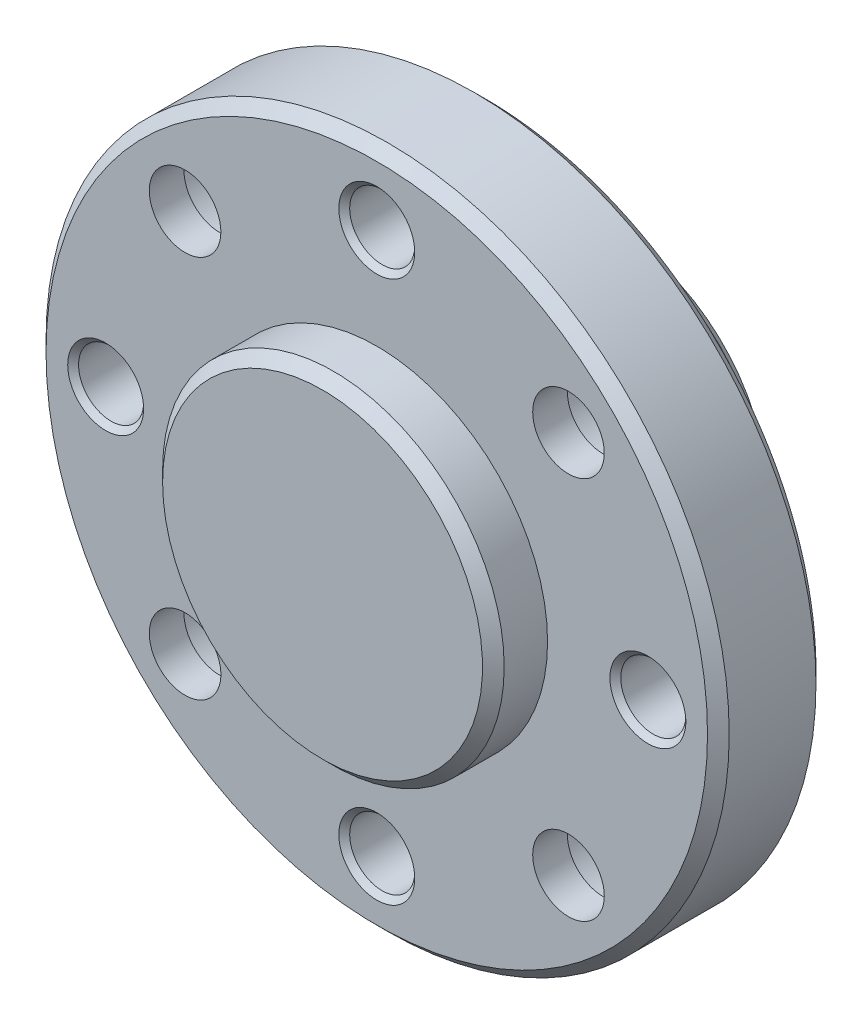
SolidWorks part; units mm, degrees
material "7050-T73510"
ref_plane "前视基准面" through (0, 0, 0) normal (0, 0, 1) x (1, 0, 0)
ref_plane "上视基准面" through (0, 0, 0) normal (0, 1, 0) x (1, 0, 0)
ref_plane "右视基准面" through (0, 0, 0) normal (1, 0, 0) x (0, 0, -1)
sketch "草图1" plane through (0, 0, 0) normal (1, 0, 0) x (0, 0, -1)
  line L0 (-27.0993, 0) -> (42.7335, 0) construction
  line L1 (0, 0) -> (0, 15.75)
  line L2 (0, 15.75) -> (5, 15.75)
  line L3 (5, 15.75) -> (5, 31.5)
  line L4 (5, 31.5) -> (15, 31.5)
  line L5 (15, 31.5) -> (15, 15)
  line L6 (15, 15) -> (27, 15)
  line L7 (27, 15) -> (27, 10)
  line L8 (27, 10) -> (3, 10)
  line L9 (3, 10) -> (3, 0)
  line L10 (3, 0) -> (0, 0)
  dimension "D1" = 31.5
  dimension "D2" = 5
  dimension "D3" = 63
  dimension "D4" = 10
  dimension "D5" = 30
  dimension "D6" = 20
  dimension "D7" = 3
  dimension "D8" = 24
revolve "旋转1" add sketch "草图1" angle 360 about L0
sketch "草图2" plane through (0, 0, -15) normal (0, 0, -1) x (-1, 0, 0)
  line L0 (-39.8585, 0) -> (40.5821, 0) construction
  line L1 (0, 34.2021) -> (0, -33.8732) construction
  line L2 (-17.6777, 17.6777) -> (0, 0) construction
  circle A0 centre (-17.6777, 17.6777) radius 5.5
  circle A1 centre (-17.6777, 17.6777) radius 3.3
  circle A2 centre (0, 0) radius 25 construction
  circle A3 centre (0, 25) radius 3
  circle A4 centre (17.6777, 17.6777) radius 5.5
  circle A5 centre (17.6777, 17.6777) radius 3.3
  circle A6 centre (17.6777, -17.6777) radius 3.3
  circle A7 centre (17.6777, -17.6777) radius 5.5
  circle A8 centre (-17.6777, -17.6777) radius 5.5
  circle A9 centre (-17.6777, -17.6777) radius 3.3
  circle A10 centre (0, -25) radius 3
  circle A11 centre (-25, 0) radius 3
  circle A12 centre (25, 0) radius 3
  dimension "D2" = 50
  dimension "D3" = 6.6
  dimension "D4" = 11
  dimension "D5" = 6
  dimension "D1" = 45
extrude "切除-拉伸1" cut sketch "草图2" against normal blind 10 contours A11 | A1 | A3 | A5 | A12 | A6 | A10 | A9
extrude "切除-拉伸2" cut sketch "草图2<3>" against normal blind 6.8 contours A0 A1 | A4 A5 | A7 A6 | A8 A9 region at (23.0221, 17.6777, -15) region at (-12.3332, 17.6777, -15) region at (-12.3332, -17.6777, -15) region at (23.0221, -17.6777, -15)
sketch "草图2<3>" plane through (0, 0, -15) normal (0, 0, -1) x (-1, 0, 0) same geometry as "草图2"
chamfer "倒角1" distance 1 angle 45 1 edges at (15.75, 0, 0)
chamfer "倒角2" distance 1 angle 45 1 edges at (10, 0, -27)
chamfer "倒角3" distance 1 angle 45 2 edges at (31.5, 0, -5) (31.5, 0, -15)
sketch "草图3" plane through (0, 0, 0) normal (0, 1, 0) x (1, 0, 0)
  line L0 (0, 35.5783) -> (0, -11.253) construction
  line L1 (15, 27) -> (-15, 27) construction
  point P3 (0, 21)
  dimension "D1" = 6
hole_wizard "M4 螺纹孔1" positions "草图4" profile "草图5" tap size "M4" standard "GB" end condition through all
sketch "草图4" plane through (0, 0, 0) normal (0, 1, 0) x (1, 0, 0)
  point P0 (0, 21)
sketch "草图5" plane through (0, 0, -21) normal (1, 0, 0) x (0, 0, -1)
  line L0 (0, 0) -> (0, 31.5)
  line L1 (0, 31.5) -> (1.65, 31.5)
  line L2 (1.65, 31.5) -> (1.65, 0)
  line L5 (1.65, 0) -> (0, 0)
  line L11 (0, -6.35) -> (0, 107.95) construction
  dimension "通孔螺纹孔钻头直径" = 3.3
  dimension "通孔螺纹孔钻头深度" = 31.5
cosmetic thread "孔螺蚊线1" parameters "D2"=4
pattern_circular "阵列(圆周)1" count 4 every 90 about axis through (0, 0, -27) along (0, 0, 1) of "M4 螺纹孔1"
chamfer "倒角4" distance 0.5 angle 45 8 edges at (-28, 0, -15) (-3, 25, -15) (-28, 0, -5) (-3, 25, -5) (28, 0, -15) (28, 0, -5) (3, -25, -15) (3, -25, -5)
chamfer "倒角5" distance 1 angle 45 1 edges at (15, 0, -27)
